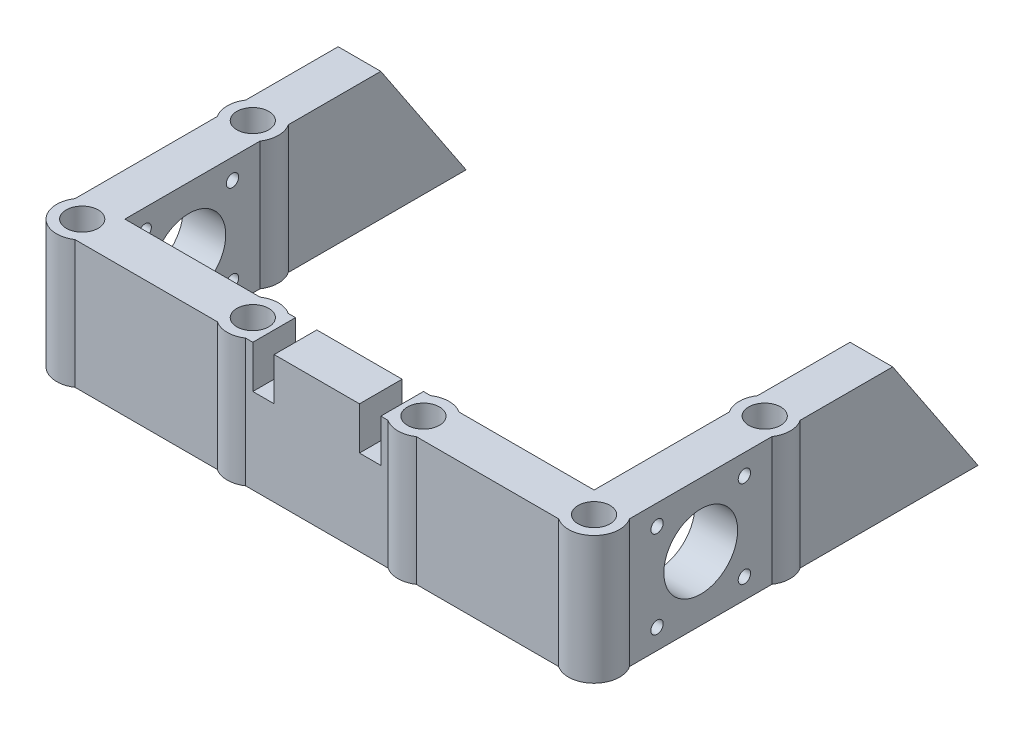
SolidWorks part; units mm, degrees
material "Custom Plastic"
ref_plane "Front Plane" through (0, 0, 0) normal (0, 0, 1) x (1, 0, 0)
ref_plane "Top Plane" through (0, 0, 0) normal (0, 1, 0) x (1, 0, 0)
ref_plane "Right Plane" through (0, 0, 0) normal (1, 0, 0) x (0, 0, -1)
sketch "Sketch4" plane through (0, 0, 0) normal (0, 1, 0) x (1, 0, 0)
  line L0 (0, 0) -> (0, -52.9379)
  line L1 (0, -114.3) -> (52.9379, -114.3) construction
  line L2 (165.1, -103.7379) -> (165.1, -61.3621)
  line L3 (165.1, 0) -> (152.4, 0)
  line L4 (152.4, 0) -> (152.4, -52.9379)
  line L5 (152.4, -101.6) -> (112.1621, -101.6)
  line L6 (12.7, -101.6) -> (12.7, -61.3621)
  line L7 (12.7, 0) -> (0, 0)
  line L8 (6.35, -107.95) -> (57.15, -107.95) construction
  line L9 (57.15, -107.95) -> (107.95, -107.95) construction
  line L10 (107.95, -107.95) -> (158.75, -107.95) construction
  line L11 (158.75, -107.95) -> (158.75, -57.15) construction
  line L12 (6.35, -107.95) -> (6.35, -57.15) construction
  line L13 (12.7, -52.9379) -> (12.7, 0)
  line L14 (0, -61.3621) -> (0, -114.3) construction
  line L15 (0, -61.3621) -> (0, -103.7379)
  line L16 (10.5621, -114.3) -> (52.9379, -114.3)
  line L17 (52.9379, -101.6) -> (12.7, -101.6)
  line L18 (61.3621, -114.3) -> (103.7379, -114.3) construction
  line L19 (61.3621, -114.3) -> (103.7379, -114.3)
  line L20 (103.7379, -101.6) -> (61.3621, -101.6)
  line L21 (112.1621, -114.3) -> (165.1, -114.3) construction
  line L22 (112.1621, -114.3) -> (154.5379, -114.3)
  line L23 (152.4, -61.3621) -> (152.4, -101.6)
  line L24 (165.1, -52.9379) -> (165.1, 0)
  circle A0 centre (6.35, -107.95) radius 4.7625
  circle A1 centre (6.35, -57.15) radius 4.7625
  circle A2 centre (57.15, -107.95) radius 4.7625
  circle A3 centre (107.95, -107.95) radius 4.7625
  circle A4 centre (158.75, -107.95) radius 4.7625
  circle A5 centre (158.75, -57.15) radius 4.7625
  arc A6 (0, -52.9379) -> (0, -61.3621) centre (6.35, -57.15) ccw
  arc A7 (12.7, -61.3621) -> (12.7, -52.9379) centre (6.35, -57.15) ccw
  arc A8 (0, -103.7379) -> (10.5621, -114.3) centre (6.35, -107.95) ccw
  arc A9 (61.3621, -101.6) -> (52.9379, -101.6) centre (57.15, -107.95) ccw
  arc A10 (52.9379, -114.3) -> (61.3621, -114.3) centre (57.15, -107.95) ccw
  arc A11 (103.7379, -114.3) -> (112.1621, -114.3) centre (107.95, -107.95) ccw
  arc A12 (112.1621, -101.6) -> (103.7379, -101.6) centre (107.95, -107.95) ccw
  arc A13 (154.5379, -114.3) -> (165.1, -103.7379) centre (158.75, -107.95) ccw
  arc A14 (152.4, -52.9379) -> (152.4, -61.3621) centre (158.75, -57.15) ccw
  arc A15 (165.1, -61.3621) -> (165.1, -52.9379) centre (158.75, -57.15) ccw
  point P30 (158.75, 0)
  dimension "D6" = 9.525
  dimension "D8" = 7.62
  dimension "D10" = 15.24
  dimension "D11" = 7.62
  dimension "D12" = 7.62
  dimension "D13" = 15.24
  dimension "D14" = 15.24
  dimension "D1" = 12.7
  dimension "D2" = 12.7
  dimension "D3" = 12.7
  dimension "D4" = 165.1
  dimension "D5" = 114.3
  dimension "D7" = 6.35
  dimension "D9" = 50.8
extrude "Boss-Extrude2" add sketch "Sketch4" along normal blind 38.1
chamfer "Chamfer2" distance 38.1 distance2 25.4 2 edges at (158.75, 38.1, 0) (6.35, 38.1, 0) first distance on face at (158.75, 19.05, 0) first distance on face at (6.35, 19.05, 0)
sketch "Sketch6" plane through (0, 0, 114.3) normal (0, 0, 1) x (1, 0, 0)
  line L0 (63.5, 38.1) -> (63.5, 25.4)
  line L1 (61.3621, 38.1) -> (103.7379, 38.1) construction
  line L2 (63.5, 25.4) -> (69.85, 25.4)
  line L3 (69.85, 25.4) -> (69.85, 38.1)
  line L4 (95.25, 38.1) -> (95.25, 25.4)
  line L5 (95.25, 25.4) -> (101.6, 25.4)
  line L6 (101.6, 25.4) -> (101.6, 38.1)
  line L7 (95.25, 38.1) -> (101.6, 38.1)
  line L8 (63.5, 38.1) -> (69.85, 38.1)
  line L9 (61.3621, 38.1) -> (63.5, 38.1) construction
  line L10 (101.6, 38.1) -> (103.7379, 38.1) construction
  dimension "D1" = 6.35
  dimension "D2" = 6.35
  dimension "D3" = 12.7
  dimension "D4" = 12.7
  dimension "D5" = 25.4
extrude "Cut-Extrude3" cut sketch "Sketch6" against normal through all
sketch "Sketch7" plane through (165.1, 0, 0) normal (1, 0, 0) x (0, 0, -1)
  line L0 (-69.55, 32.05) -> (-95.55, 6.05) construction
  line L1 (-69.55, 32.05) -> (-69.55, 6.05) construction
  line L2 (-69.55, 6.05) -> (-95.55, 6.05) construction
  line L3 (-95.55, 6.05) -> (-95.55, 32.05) construction
  line L4 (-95.55, 32.05) -> (-69.55, 32.05) construction
  line L6 (-115.57, 38.1) -> (-115.57, 0) construction
  line L7 (-115.57, 19.05) -> (-82.55, 19.05) construction
  line L8 (-82.55, 19.05) -> (-82.55, 38.1) construction
  line L9 (-103.7379, 38.1) -> (-61.3621, 38.1) construction
  circle A0 centre (-82.55, 19.05) radius 10.9855
  circle A1 centre (-69.55, 32.05) radius 1.8415
  circle A2 centre (-69.55, 6.05) radius 1.8415
  circle A3 centre (-95.55, 6.05) radius 1.8415
  circle A4 centre (-95.55, 32.05) radius 1.8415
  dimension "D2" = 21.971
  dimension "D3" = 3.683
  dimension "D1" = 26
extrude "Cut-Extrude4" cut sketch "Sketch7" against normal through all
